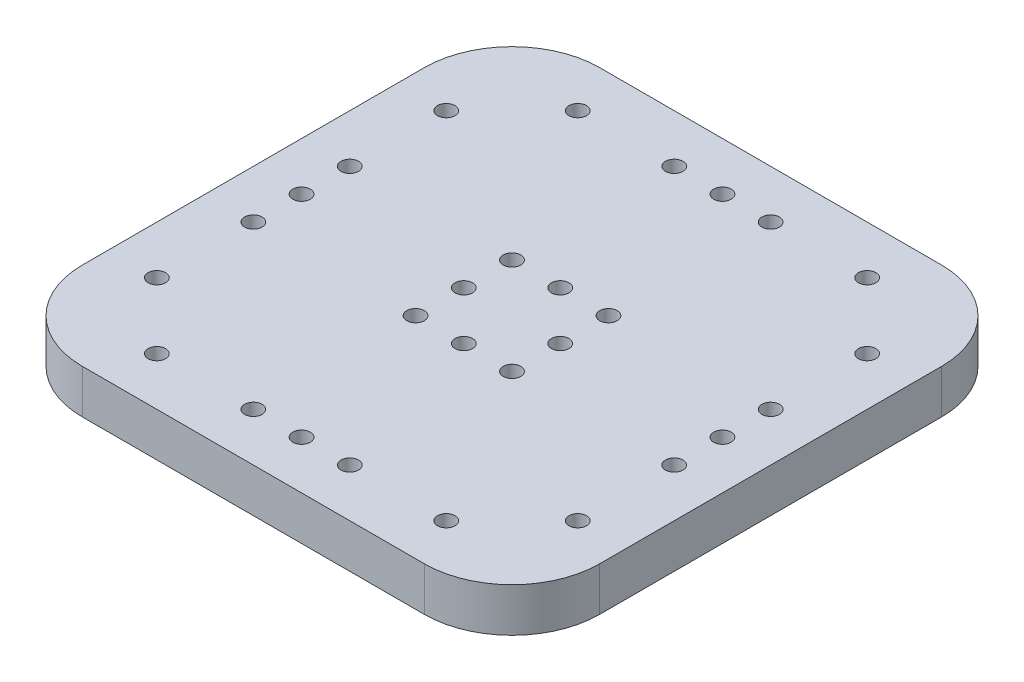
SolidWorks part; units mm, degrees
ref_plane "Front Plane" through (0, 0, 0) normal (0, 0, 1) x (1, 0, 0)
ref_plane "Top Plane" through (0, 0, 0) normal (0, 1, 0) x (1, 0, 0)
ref_plane "Right Plane" through (0, 0, 0) normal (1, 0, 0) x (0, 0, -1)
sketch "Sketch1" plane through (0, 0, 0) normal (0, 1, 0) x (1, 0, 0)
  line L0 (-1.371, 1.1217) -> (-1.371, -46.8783) construction
  line L1 (-12.371, -46.8783) -> (9.629, -46.8783) construction
  line L2 (9.629, -46.8783) -> (31.629, -46.8783) construction
  line L3 (-12.371, -46.8783) -> (-34.371, -46.8783) construction
  line L4 (-1.371, 1.1217) -> (-1.371, -9.8783) construction
  line L5 (-12.371, -9.8783) -> (9.629, -9.8783) construction
  line L6 (-1.371, 1.1217) -> (-12.371, 1.1217) construction
  line L7 (-12.371, 49.1217) -> (-34.371, 49.1217) construction
  line L8 (9.629, 49.1217) -> (31.629, 49.1217) construction
  line L9 (-12.371, 49.1217) -> (9.629, 49.1217) construction
  line L10 (-60.371, 60.1217) -> (57.629, -57.8783) construction
  line L11 (46.629, 12.1217) -> (46.629, 34.1217) construction
  line L12 (46.629, -9.8783) -> (46.629, -31.8783) construction
  line L13 (46.629, 12.1217) -> (46.629, -9.8783) construction
  line L14 (-49.371, 12.1217) -> (-49.371, -9.8783) construction
  line L15 (-49.371, -9.8783) -> (-49.371, -31.8783) construction
  line L16 (-49.371, 12.1217) -> (-49.371, 34.1217) construction
  line L18 (-60.371, 60.1217) -> (57.629, 60.1217)
  line L19 (-60.371, 60.1217) -> (-60.371, -57.8783)
  line L20 (-60.371, -57.8783) -> (57.629, -57.8783)
  line L21 (57.629, 60.1217) -> (57.629, -57.8783)
  line L22 (-60.371, 60.1217) -> (57.629, -57.8783) construction
  line L23 (-60.371, -57.8783) -> (57.629, 60.1217) construction
  circle A0 centre (-1.371, -46.8783) radius 2
  circle A1 centre (9.629, -46.8783) radius 2
  circle A2 centre (31.629, -46.8783) radius 2
  circle A3 centre (-34.371, -46.8783) radius 2
  circle A4 centre (-12.371, -46.8783) radius 2
  circle A5 centre (-1.371, -9.8783) radius 2
  circle A6 centre (9.629, -9.8783) radius 2
  circle A7 centre (-12.371, -9.8783) radius 2
  circle A8 centre (-12.371, 1.1217) radius 2
  circle A9 centre (-12.371, 12.1217) radius 2
  circle A10 centre (9.629, 12.1217) radius 2
  circle A11 centre (-1.371, 12.1217) radius 2
  circle A12 centre (-12.371, 49.1217) radius 2
  circle A13 centre (-34.371, 49.1217) radius 2
  circle A14 centre (31.629, 49.1217) radius 2
  circle A15 centre (9.629, 49.1217) radius 2
  circle A16 centre (-1.371, 49.1217) radius 2
  circle A17 centre (9.629, 1.1217) radius 2
  circle A18 centre (46.629, 12.1217) radius 2
  circle A19 centre (46.629, 34.1217) radius 2
  circle A20 centre (46.629, -31.8783) radius 2
  circle A21 centre (46.629, -9.8783) radius 2
  circle A22 centre (46.629, 1.1217) radius 2
  circle A23 centre (-49.371, 1.1217) radius 2
  circle A24 centre (-49.371, -9.8783) radius 2
  circle A25 centre (-49.371, -31.8783) radius 2
  circle A26 centre (-49.371, 34.1217) radius 2
  circle A27 centre (-49.371, 12.1217) radius 2
  dimension "D1" = 48
  dimension "D2" = 11
  dimension "D3" = 22
  dimension "D4" = 11
extrude "Boss-Extrude1" add sketch "Sketch1" along normal blind 10
fillet "Fillet1" radius 20 4 edges at (-60.371, 5, -60.1217) (57.629, 5, -60.1217) (57.629, 5, 57.8783) (-60.371, 5, 57.8783)
ref_plane "Plane1" through (0, 0, -1.1217) normal (0, 0, 1) x (1, 0, 0)
ref_plane "Plane2" through (-1.371, 0, 0) normal (1, 0, 0) x (0, 0, -1)
sketch "Sketch2" plane through (0, 10, 0) normal (0, 1, 0) x (1, 0, 0)
  line L0 (-60.371, -37.8783) -> (-40.7529, -37.8783)
  line L1 (-40.7529, -37.8783) -> (-40.7529, 172.1217)
  line L2 (-40.7529, 67.1217) -> (-60.371, 67.1217) construction
  line L3 (-60.371, 172.1217) -> (-40.7529, 172.1217)
  line L4 (37.629, 60.1217) -> (-40.371, 60.1217)
  line L5 (-60.371, 40.1217) -> (-60.371, -37.8783)
  line L6 (-40.371, -57.8783) -> (37.629, -57.8783)
  line L7 (57.629, -37.8783) -> (57.629, 40.1217)
  line L9 (-60.371, 172.1217) -> (-60.371, -37.8783)
  circle A0 centre (-49.371, -31.8783) radius 2 construction
  arc A4 (-40.371, 60.1217) -> (-60.371, 40.1217) centre (-40.371, 40.1217) ccw
  arc A5 (-60.371, -37.8783) -> (-40.371, -57.8783) centre (-40.371, -37.8783) ccw
  arc A6 (37.629, -57.8783) -> (57.629, -37.8783) centre (37.629, -37.8783) ccw
  arc A7 (57.629, 40.1217) -> (37.629, 60.1217) centre (37.629, 40.1217) ccw
  circle A15 centre (-49.371, 34.1217) radius 2 construction
  circle A16 centre (-49.371, -31.8783) radius 2
  circle A23 centre (-49.371, 34.1217) radius 2
  circle A24 centre (-49.371, 166.1217) radius 2
  circle A25 centre (-49.371, 100.1217) radius 2
  dimension "D2" = 105
  dimension "D1" = 0
